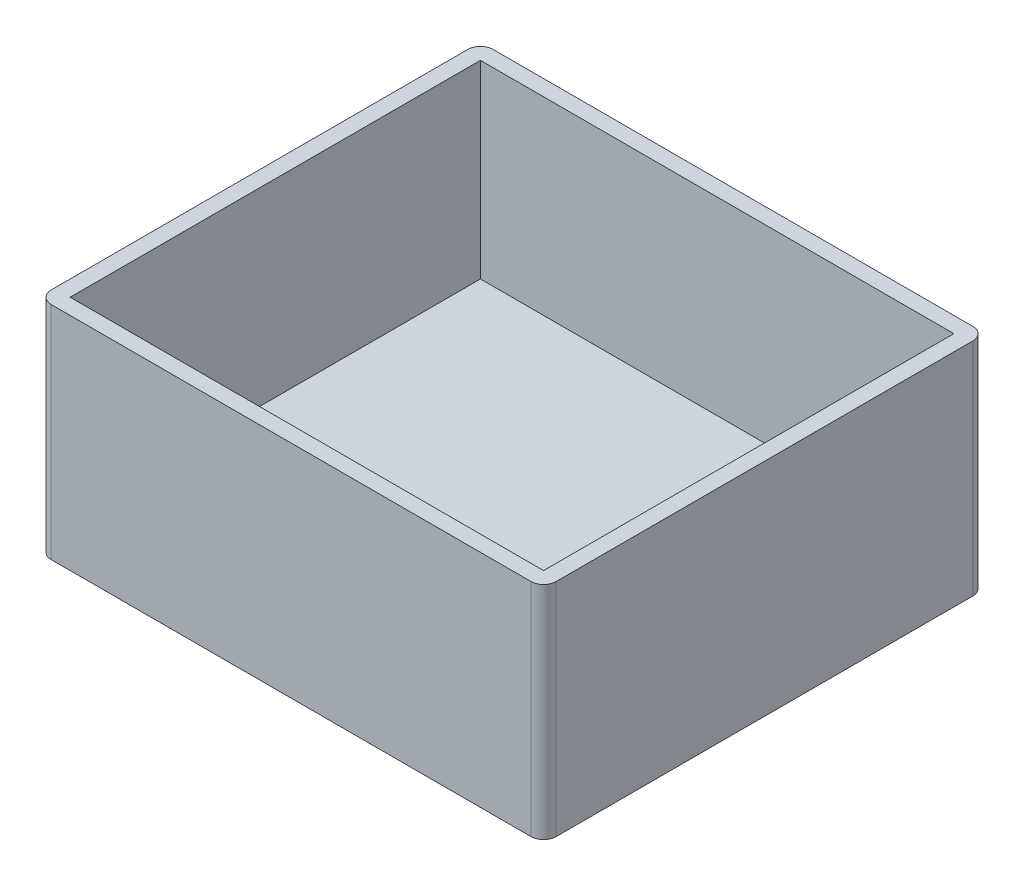
SolidWorks part; units mm, degrees
ref_plane "Front Plane" through (0, 0, 0) normal (0, 0, 1) x (1, 0, 0)
ref_plane "Top Plane" through (0, 0, 0) normal (0, 1, 0) x (1, 0, 0)
ref_plane "Right Plane" through (0, 0, 0) normal (1, 0, 0) x (0, 0, -1)
sketch "Sketch1" plane through (0, 0, 0) normal (0, 1, 0) x (1, 0, 0)
  line L1 (39.9638, -57.9788) -> (-40.0362, -57.9788)
  line L2 (39.9638, -57.9788) -> (39.9638, 12.0212)
  line L3 (39.9638, 12.0212) -> (-40.0362, 12.0212)
  line L4 (-40.0362, -57.9788) -> (-40.0362, 12.0212)
  line L5 (39.9638, -57.9788) -> (-40.0362, 12.0212) construction
  line L6 (39.9638, 12.0212) -> (-40.0362, -57.9788) construction
  point P0 (-0.0362, -22.9788)
extrude "Boss-Extrude1" add sketch "Sketch1" along normal blind 35
sketch "Sketch2" plane through (0, 35, 0) normal (0, 1, 0) x (1, 0, 0)
  line L0 (-0.0362, 12.0212) -> (-0.0362, -57.9788) construction
  line L1 (39.9638, 12.0212) -> (-40.0362, 12.0212) construction
  line L2 (-40.0362, -57.9788) -> (39.9638, -57.9788) construction
sketch "Sketch3" plane through (0, 35, 0) normal (0, 1, 0) x (1, 0, 0)
  line L4 (-37.5362, -55.4788) -> (37.4638, -55.4788)
  line L5 (-37.5362, -55.4788) -> (-37.5362, 9.5212)
  line L6 (-37.5362, 9.5212) -> (37.4638, 9.5212)
  line L7 (37.4638, -55.4788) -> (37.4638, 9.5212)
  line L8 (-37.5362, -55.4788) -> (37.4638, 9.5212) construction
  line L9 (-37.5362, 9.5212) -> (37.4638, -55.4788) construction
  point P6 (-0.0362, -22.9788)
extrude "Cut-Extrude1" cut sketch "Sketch3" against normal blind 30
fillet "Fillet2" radius 2 4 edges at (-40.0362, 17.5, 57.9788) (39.9638, 17.5, 57.9788) (39.9638, 17.5, -12.0212) (-40.0362, 17.5, -12.0212)
sketch "Sketch4" plane through (0, 5, 0) normal (0, 1, 0) x (1, 0, 0)
  line L0 (-0.0362, 9.5212) -> (-0.0362, -55.4788) construction
  line L1 (37.4638, 9.5212) -> (-37.5362, 9.5212) construction
  line L2 (-37.5362, -55.4788) -> (37.4638, -55.4788) construction
  line L3 (-0.0362, -55.4788) -> (-0.0362, -22.9788) construction
  line L4 (-27.6762, -28.6799) -> (-18.7862, -28.6799) construction
  line L5 (-9.8962, -5.9025) -> (-9.8962, -51.4573)
  line L7 (-18.7862, -22.9788) -> (-18.7862, 9.5212)
  line L8 (-18.7862, 9.5212) -> (-18.7862, -55.4788)
  line L10 (-27.6762, -5.9025) -> (-27.6762, -51.4573)
  circle A0 centre (-9.8962, -51.4573) radius 2.5
  circle A1 centre (-9.8962, -5.9025) radius 2.5
